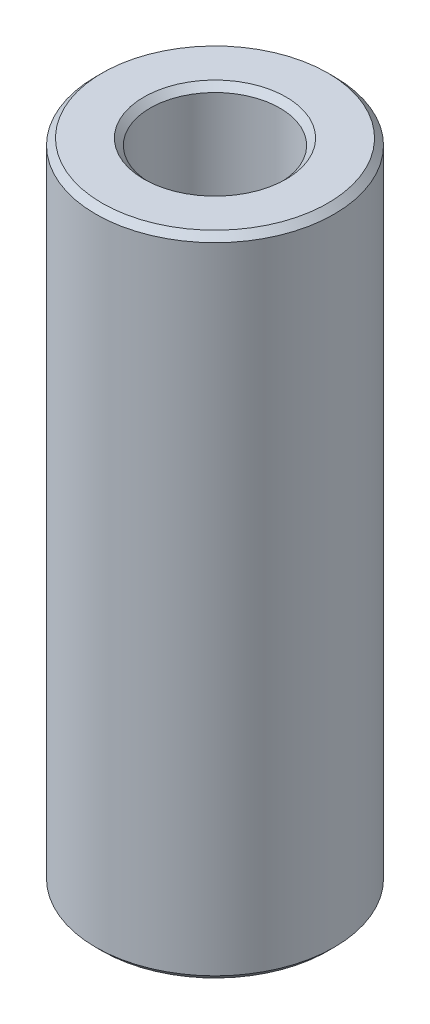
SolidWorks part; units mm, degrees
ref_plane "Front Plane" through (0, 0, 0) normal (0, 0, 1) x (1, 0, 0)
ref_plane "Top Plane" through (0, 0, 0) normal (0, 1, 0) x (1, 0, 0)
ref_plane "Right Plane" through (0, 0, 0) normal (1, 0, 0) x (0, 0, -1)
sketch "Sketch1" plane through (0, 0, 0) normal (0, 1, 0) x (1, 0, 0)
  circle A0 centre (0, 0) radius 57.5
  dimension "SLEEVE_OD" = 115
extrude "Boss-Extrude1" add sketch "Sketch1" along normal blind 312.4987
sketch "Sketch2" plane through (0, 0, 0) normal (0, 1, 0) x (1, 0, 0)
  circle A0 centre (0, 0) radius 31.2826
  dimension "BORE_D" = 62.5652
extrude "Cut-Extrude1" cut sketch "Sketch2" along normal through all
chamfer "Chamfer1" distance 3.0587 angle 45 4 edges at (0, 312.4987, 31.2826) (0, 0, 31.2826) (0, 0, 57.5) (0, 312.4987, 57.5)
